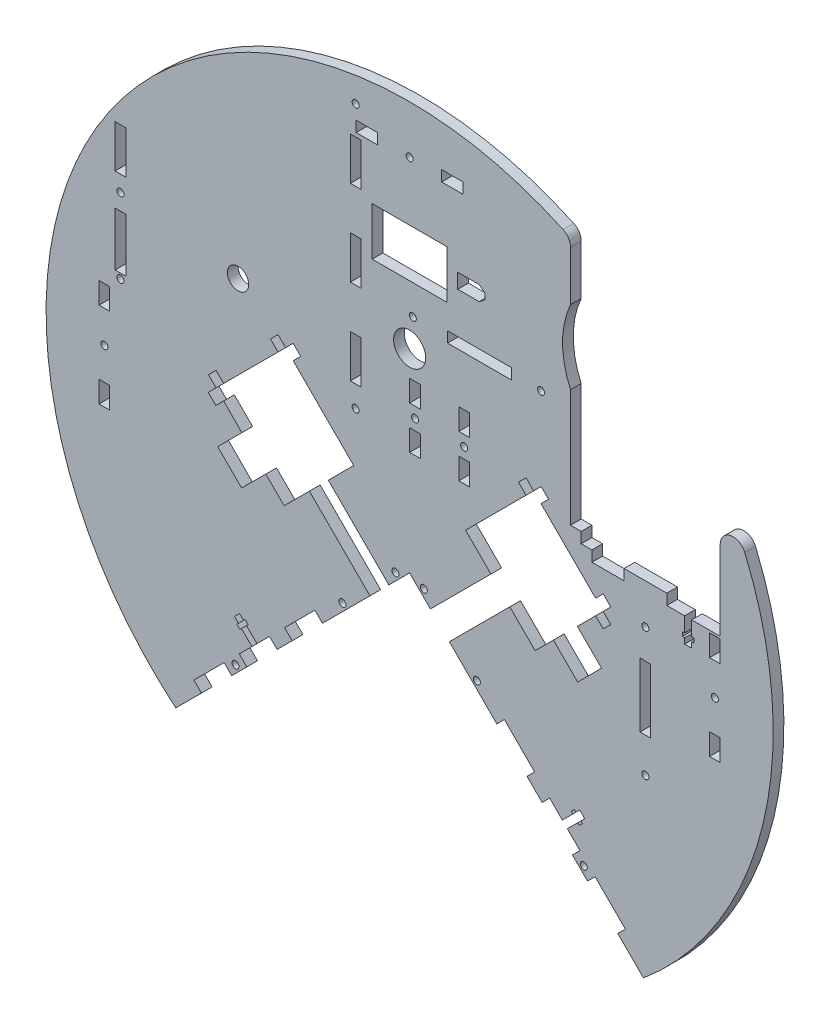
SolidWorks part; units mm, degrees
ref_plane "Front Plane" through (0, 0, 0) normal (0, 0, 1) x (1, 0, 0)
ref_plane "Top Plane" through (0, 0, 0) normal (0, 1, 0) x (1, 0, 0)
ref_plane "Right Plane" through (0, 0, 0) normal (1, 0, 0) x (0, 0, -1)
sketch "Sketch1" plane through (0, 0, 0) normal (0, 0, 1) x (1, 0, 0)
  circle A0 centre (0, 0) radius 215.9
  dimension "D1" = 431.8
extrude "Boss-Extrude1" add sketch "Sketch1" along normal blind 6.35 contours A0
sketch "Sketch2" plane through (0, 0, 0) normal (0, 0, -1) x (-1, 0, 0)
  line L0 (0, -26.4411) -> (138.8703, -165.3114)
  line L2 (0, -26.4411) -> (-138.8703, -165.3114)
  line L3 (-134.0557, -160.4967) -> (-35.731, -62.1721) construction
  line L4 (0, 0) -> (0, -240.5018) construction
  arc A4 (-138.8703, -165.3114) -> (138.8703, -165.3114) centre (0, 0) ccw
  circle A5 centre (0, 0) radius 215.9 construction
  dimension "D1" = 90
extrude "Cut-Extrude1" cut sketch "Sketch2" against normal through all
sketch "Sketch3" plane through (0, 0, 6.35) normal (0, 0, 1) x (1, 0, 0)
  line L0 (73.6381, 52.5852) -> (114.9473, 11.276)
  line L1 (73.6381, 52.5852) -> (33.2269, 12.174)
  line L2 (114.9473, 11.276) -> (74.5361, -29.1352)
  line L3 (33.2269, 12.174) -> (74.5361, -29.1352)
  line L4 (74.5361, -29.1352) -> (70.046, -24.645) construction
  line L5 (97.2507, 34.8885) -> (46.1575, -16.2046) construction
  line L6 (48.2689, -2.8679) -> (59.4942, -14.0932)
  line L7 (48.2689, -2.8679) -> (12.3479, -38.7889)
  line L8 (59.4942, -14.0932) -> (23.5732, -50.0143)
  line L9 (12.3479, -38.7889) -> (23.5732, -50.0143)
  line L10 (88.68, 15.0926) -> (77.4547, 26.3179) construction
  line L11 (0, -26.4411) -> (138.8703, -165.3114) construction
  line M8 (0, -26.4411) -> (138.8703, -165.3114)
extrude "Cut-Extrude2" cut sketch "Sketch3" against normal through all contours L8 L6 L3 L7 M8 | L0 L5 L6 L3 L2 | L5 L0 L1 L3 region at (63.7598, 22.0523, 6.35) region at (84.4144, 1.3977, 6.35) region at (35.921, -26.4411, 6.35)
mirror "Mirror1" about plane through (0, 0, 0) normal (1, 0, 0) of "Cut-Extrude2"
sketch "Sketch4" plane through (0, 0, 6.35) normal (0, 0, 1) x (1, 0, 0)
  line L0 (-178.0884, 19.05) -> (-178.0884, 31.75) construction
  line L1 (178.0884, -19.05) -> (184.4384, -19.05)
  line L2 (178.0884, -19.05) -> (178.0884, -31.75)
  line L3 (178.0884, -31.75) -> (184.4384, -31.75)
  line L4 (184.4384, -19.05) -> (184.4384, -31.75)
  line L5 (178.0884, 31.75) -> (184.4384, 31.75)
  line L6 (178.0884, 31.75) -> (178.0884, 19.05)
  line L7 (178.0884, 19.05) -> (184.4384, 19.05)
  line L8 (184.4384, 31.75) -> (184.4384, 19.05)
  line L9 (178.0884, -19.05) -> (184.4384, -19.05)
  line L10 (178.0884, -19.05) -> (178.0884, -31.75)
  line L11 (178.0884, -31.75) -> (184.4384, -31.75)
  line L12 (184.4384, -19.05) -> (184.4384, -31.75)
  line L13 (-184.4384, 31.75) -> (-178.0884, 31.75)
  line L14 (-184.4384, 31.75) -> (-184.4384, 19.05)
  line L15 (-184.4384, 19.05) -> (-178.0884, 19.05)
  line L16 (-178.0884, 31.75) -> (-178.0884, 19.05)
  line L18 (-184.4384, -19.05) -> (-178.0884, -19.05)
  line L19 (-184.4384, -19.05) -> (-184.4384, -31.75)
  line L20 (-184.4384, -31.75) -> (-178.0884, -31.75)
  line L21 (-178.0884, -19.05) -> (-178.0884, -31.75)
extrude "Cut-Extrude3" cut sketch "Sketch4" against normal through all contours L21 L18 L19 L20 | L8 L5 L6 L7 | L4 L1 L2 L3 | L14 L15 L16 L13 region at (181.2634, -25.4, 6.35) region at (181.2634, 25.4, 6.35) region at (-181.2634, -25.4, 6.35)
sketch "Sketch5" plane through (0, 0, 6.35) normal (0, 0, 1) x (1, 0, 0)
  line L0 (-128.1057, -145.5666) -> (-110.1452, -127.6061)
  line L1 (-110.1452, -127.6061) -> (-105.6551, -132.0962)
  line L2 (-138.8703, -165.3114) -> (-23.5732, -50.0143) construction
  line L3 (-105.6551, -132.0962) -> (-110.1452, -127.6061) construction
  line L4 (-105.6551, -132.0962) -> (-123.6156, -150.0567)
  line L5 (-128.1057, -145.5666) -> (-123.6156, -150.0567) construction
  line L6 (-123.6156, -150.0567) -> (-128.1057, -145.5666)
extrude "Cut-Extrude4" cut sketch "Sketch5" against normal blind 6.35
pattern_linear "LPattern1" count 3 spacing 38.1 along (0.7071, 0.7071, 0) of "Cut-Extrude4"
sketch "Sketch6" plane through (0, 0, 6.35) normal (0, 0, 1) x (1, 0, 0)
  line L0 (110.1452, -127.6061) -> (128.1057, -145.5666)
  line L1 (128.1057, -145.5666) -> (123.6156, -150.0567)
  line L2 (23.5732, -50.0143) -> (138.8703, -165.3114) construction
  line L3 (123.6156, -150.0567) -> (128.1057, -145.5666) construction
  line L4 (123.6156, -150.0567) -> (105.6551, -132.0962)
  line L5 (110.1452, -127.6061) -> (105.6551, -132.0962) construction
  line L6 (105.6551, -132.0962) -> (110.1452, -127.6061)
extrude "Cut-Extrude5" cut sketch "Sketch6" against normal blind 6.35
pattern_linear "LPattern2" count 3 spacing 38.1 along (-0.7071, 0.7071, 0) of "Cut-Extrude5"
sketch "Sketch8" plane through (0, 0, 0) normal (0, 0, -1) x (-1, 0, 0)
  line L0 (174.9134, 48.3833) -> (174.9134, 73.7833) construction
  line L1 (28.8634, 181.7333) -> (35.2134, 181.7333)
  line L2 (28.8634, 181.7333) -> (28.8634, 156.3333)
  line L3 (28.8634, 156.3333) -> (35.2134, 156.3333)
  line L4 (35.2134, 181.7333) -> (35.2134, 156.3333)
  line L5 (28.8634, 130.9333) -> (35.2134, 130.9333)
  line L6 (28.8634, 130.9333) -> (28.8634, 105.5333)
  line L7 (28.8634, 105.5333) -> (35.2134, 105.5333)
  line L8 (35.2134, 130.9333) -> (35.2134, 105.5333)
  line L9 (28.8634, 80.1333) -> (35.2134, 80.1333)
  line L10 (28.8634, 80.1333) -> (28.8634, 54.7333)
  line L11 (28.8634, 54.7333) -> (35.2134, 54.7333)
  line L12 (35.2134, 80.1333) -> (35.2134, 54.7333)
  line L13 (168.5634, 118.2333) -> (174.9134, 118.2333)
  line L14 (168.5634, 118.2333) -> (168.5634, 92.8333)
  line L15 (168.5634, 92.8333) -> (174.9134, 92.8333)
  line L16 (174.9134, 118.2333) -> (174.9134, 92.8333)
  line L17 (168.5634, 73.7833) -> (174.9134, 73.7833)
  line L18 (168.5634, 73.7833) -> (168.5634, 41.9385)
  line L19 (168.5634, 41.9385) -> (174.9134, 41.9385)
  line L20 (174.9134, 73.7833) -> (174.9134, 41.9385)
extrude "Cut-Extrude7" cut sketch "Sketch8" against normal through all
sketch "Sketch11" plane through (0, 0, 0) normal (0, 0, -1) x (-1, 0, 0)
  line L0 (184.4384, 2.1209) -> (178.0884, -2.1209) construction
  line L1 (184.4384, -2.1209) -> (178.0884, 2.1209) construction
  circle A0 centre (181.2634, 0) radius 2.0955
  dimension "D1" = 4.191
extrude "Wheel Hole" cut sketch "Sketch11" against normal through all
mirror "Mirror2" about plane through (0, 0, 0) normal (1, 0, 0) of "Wheel Hole"
sketch "Sketch12" plane through (0, 0, 6.35) normal (0, 0, 1) x (1, 0, 0)
  line L0 (0, 0) -> (0, 252.4228) construction
  line L1 (22.225, 123.825) -> (-22.225, 123.825)
  line L2 (22.225, 123.825) -> (22.225, 152.4)
  line L3 (22.225, 152.4) -> (-22.225, 152.4)
  line L4 (-22.225, 123.825) -> (-22.225, 152.4)
  arc A0 (138.8703, -165.3114) -> (-138.8703, -165.3114) centre (0, 0) ccw construction
  dimension "D3" = 152.4
  dimension "D1" = 28.575
  dimension "D2" = 44.45
extrude "Battery hole" cut sketch "Sketch12" against normal through all
sketch "Sketch13" plane through (0, 0, 0) normal (0, 0, -1) x (-1, 0, 0)
  line L0 (107.1638, -124.6246) -> (99.6563, -126.0974) construction
  line L1 (104.1464, -121.6073) -> (99.6563, -126.0974) construction
  line L2 (138.8703, -165.3114) -> (123.6156, -150.0567) construction
  line L3 (104.1464, -121.6073) -> (102.6737, -129.1148) construction
  line L4 (107.1638, -124.6246) -> (102.6737, -129.1148) construction
  line L5 (36.1647, -62.6058) -> (43.6722, -61.133) construction
  line L6 (51.7736, -78.2147) -> (23.5732, -50.0143) construction
  line L7 (40.6548, -58.1157) -> (36.1647, -62.6058) construction
  line L8 (39.1821, -65.6231) -> (40.6548, -58.1157) construction
  line L9 (43.6722, -61.133) -> (39.1821, -65.6231) construction
  line L10 (4.6652, -31.1063) -> (12.1727, -29.6336) construction
  line L11 (12.3479, -38.7889) -> (0, -26.4411) construction
  line L12 (9.1554, -26.6162) -> (4.6652, -31.1063) construction
  line L13 (7.6826, -34.1237) -> (9.1554, -26.6162) construction
  line L14 (12.1727, -29.6336) -> (7.6826, -34.1237) construction
  circle A0 centre (103.41, -125.361) radius 2.0955
  circle A1 centre (39.9184, -61.8694) radius 2.0955
  circle A2 centre (8.419, -30.37) radius 2.0955
  dimension "D1" = 4.191
extrude "Cut-Extrude10" cut sketch "Sketch13" against normal through all
mirror "Mirror3" about plane through (0, 0, 0) normal (1, 0, 0) of "Cut-Extrude10"
sketch "Sketch14" plane through (0, 0, 6.35) normal (0, 0, 1) x (1, 0, 0)
  line L0 (-174.9134, 85.4419) -> (-168.5634, 81.1747) construction
  line L1 (-168.5634, 85.4419) -> (-174.9134, 81.1747) construction
  line L2 (-174.9134, 40.9919) -> (-168.5634, 36.7247) construction
  line L3 (-174.9134, 36.7247) -> (-168.5634, 40.9919) construction
  circle A0 centre (-171.7384, 83.3083) radius 2.0955
  circle A1 centre (-171.7384, 38.8583) radius 2.0955
  dimension "D1" = 4.191
extrude "Cut-Extrude11" cut sketch "Sketch14" against normal through all
sketch "Sketch15" plane through (0, 0, 6.35) normal (0, 0, 1) x (1, 0, 0)
  line L0 (-28.8634, 44.1669) -> (-35.2134, 39.8997) construction
  line L1 (-35.2134, 44.1669) -> (-28.8634, 39.8997) construction
  line L2 (-35.2134, 200.9503) -> (-28.8634, 196.6831) construction
  line L3 (-28.8634, 200.9503) -> (-35.2134, 196.6831) construction
  circle A0 centre (-32.0384, 42.0333) radius 2.0955
  circle A1 centre (-32.0384, 198.8167) radius 2.0955
  dimension "D1" = 4.191
extrude "Cut-Extrude12" cut sketch "Sketch15" against normal through all
ref_axis "Axis1" through (0, 0, 465.2086) along (0, 0, -1)
sketch "Sketch21" plane through (0, 0, 6.35) normal (0, 0, 1) x (1, 0, 0)
  line L0 (36.8153, 138.1125) -> (56.9261, 138.1125) construction
  line L1 (22.225, 152.4) -> (-22.225, 152.4) construction
  line L2 (-22.225, 123.825) -> (22.225, 123.825) construction
  line L3 (41.275, 142.494) -> (44.831, 139.7953)
  line L4 (28.575, 142.494) -> (41.275, 142.494)
  line L5 (28.575, 142.494) -> (28.575, 133.731)
  line L6 (28.575, 133.731) -> (41.275, 133.731)
  line L7 (41.275, 142.494) -> (41.275, 133.731)
  line L8 (44.831, 139.7953) -> (44.831, 136.4297)
  line L9 (44.831, 136.4297) -> (41.275, 133.731)
  line L10 (22.225, 123.825) -> (22.225, 152.4) construction
  dimension "D1" = 8.763
  dimension "D2" = 12.7
  dimension "D3" = 3.3655
  dimension "D4" = 16.256
  dimension "D5" = 6.35
extrude "XT60BatteryHole" cut sketch "Sketch21" against normal through all contours L7 L4 L5 L6 | L9 L8 L3 L7 | L7 L0 L8 L3 region at (42.7892, 139.7286, 6.35) region at (34.925, 138.1125, 6.35) region at (42.7892, 136.4964, 6.35)
sketch "Sketch22" plane through (0, 0, 6.35) normal (0, 0, 1) x (1, 0, 0)
  line L0 (0, 0) -> (0, 99.9362) construction
  line L1 (-53.4325, 88.9) -> (53.4325, 88.9) construction
  circle A0 centre (0, 88.9) radius 9.525
  dimension "D1" = 19.05
  dimension "D2" = 88.9
extrude "Wire Hole for Servo and Top Comps." cut sketch "Sketch22" against normal through all
sketch "Sketch23" plane through (0, 0, 0) normal (0, 0, -1) x (-1, 0, 0)
  line L1 (-35.56, 35.56) -> (-29.21, 35.56)
  line L2 (-35.56, 35.56) -> (-35.56, 48.26)
  line L3 (-35.56, 48.26) -> (-29.21, 48.26)
  line L4 (-29.21, 35.56) -> (-29.21, 48.26)
  line L5 (-35.56, 60.96) -> (-29.21, 60.96)
  line L6 (-35.56, 60.96) -> (-35.56, 73.66)
  line L7 (-35.56, 73.66) -> (-29.21, 73.66)
  line L8 (-29.21, 60.96) -> (-29.21, 73.66)
  line L9 (-6.35, 35.56) -> (0, 35.56)
  line L10 (-6.35, 35.56) -> (-6.35, 48.26)
  line L11 (-6.35, 48.26) -> (0, 48.26)
  line L12 (0, 35.56) -> (0, 48.26)
  line L13 (-6.35, 60.96) -> (0, 60.96)
  line L14 (-6.35, 60.96) -> (-6.35, 73.66)
  line L15 (-6.35, 73.66) -> (0, 73.66)
  line L16 (0, 60.96) -> (0, 73.66)
extrude "CameraMountTabHoles" cut sketch "Sketch23" against normal through all
sketch "Sketch24" plane through (0, 0, 6.35) normal (0, 0, 1) x (1, 0, 0)
  line L0 (29.21, 56.7436) -> (35.56, 52.4764) construction
  line L1 (29.21, 52.4764) -> (35.56, 56.7436) construction
  line L2 (0, 56.7436) -> (6.35, 52.4764) construction
  line L3 (6.35, 56.7436) -> (0, 52.4764) construction
  circle A0 centre (32.385, 54.61) radius 2.0955
  circle A1 centre (3.175, 54.61) radius 2.0955
  dimension "D1" = 4.191
extrude "Cut-Extrude18" cut sketch "Sketch24" against normal through all
sketch "Sketch25" plane through (0, 0, 6.35) normal (0, 0, 1) x (1, 0, 0)
  line L1 (-31.75, 190.5) -> (-19.05, 190.5)
  line L2 (-31.75, 190.5) -> (-31.75, 184.15)
  line L3 (-31.75, 184.15) -> (-19.05, 184.15)
  line L4 (-19.05, 190.5) -> (-19.05, 184.15)
  line L5 (19.05, 190.5) -> (31.75, 190.5)
  line L6 (19.05, 190.5) -> (19.05, 184.15)
  line L7 (19.05, 184.15) -> (31.75, 184.15)
  line L8 (31.75, 190.5) -> (31.75, 184.15)
extrude "Cut-Extrude19" cut sketch "Sketch25" against normal through all
sketch "Sketch26" plane through (0, 0, 0) normal (0, 0, -1) x (-1, 0, 0)
  line L0 (-2.1336, 184.15) -> (2.1336, 190.5) construction
  line L1 (-2.1336, 190.5) -> (2.1336, 184.15) construction
  circle A0 centre (0, 187.325) radius 2.0955
  dimension "D1" = 4.191
extrude "Cut-Extrude20" cut sketch "Sketch26" against normal through all
sketch "Sketch27" plane through (0, 0, 6.35) normal (0, 0, 1) x (1, 0, 0)
  line L0 (167.1371, -38.3935) -> (160.7871, -34.1263) construction
  line L1 (167.1371, -34.1263) -> (160.7871, -38.3935) construction
  line L2 (167.1371, 58.5607) -> (160.7871, 62.8279) construction
  line L3 (167.1371, 62.8279) -> (160.7871, 58.5607) construction
  circle A0 centre (163.9621, 60.6943) radius 2.0955
  circle A1 centre (163.9621, -36.2599) radius 2.0955
  dimension "D1" = 4.191
extrude "Cut-Extrude21" [suppressed] cut sketch "Sketch27" against normal through all
sketch "Sketch28" plane through (0, 0, 6.35) normal (0, 0, 1) x (1, 0, 0)
  line L0 (28.2358, 111.125) -> (23.9686, 104.775) construction
  line L1 (23.9686, 111.125) -> (28.2358, 104.775) construction
  line L2 (125.19, 111.125) -> (120.9228, 104.775) construction
  line L3 (120.9228, 111.125) -> (125.19, 104.775) construction
  circle A0 centre (123.0564, 107.95) radius 2.0955
  circle A1 centre (26.1022, 107.95) radius 2.0955
  dimension "D1" = 4.191
extrude "Cut-Extrude22" [suppressed] cut sketch "Sketch28" against normal through all
sketch "Sketch29" plane through (0, 0, 0) normal (0, 0, -1) x (-1, 0, 0)
  line L1 (-167.1371, -11.1125) -> (-160.7871, -11.1125)
  line L2 (-167.1371, -11.1125) -> (-167.1371, 26.9875)
  line L3 (-167.1371, 26.9875) -> (-160.7871, 26.9875)
  line L4 (-160.7871, -11.1125) -> (-160.7871, 26.9875)
  line L5 (-89.3496, 111.125) -> (-51.2496, 111.125)
  line L6 (-89.3496, 111.125) -> (-89.3496, 104.775)
  line L7 (-89.3496, 104.775) -> (-51.2496, 104.775)
  line L8 (-51.2496, 111.125) -> (-51.2496, 104.775)
extrude "Cut-Extrude23" [suppressed] cut sketch "Sketch29" against normal through all
sketch "Sketch30" plane through (0, 0, 6.35) normal (0, 0, 1) x (1, 0, 0)
  line L0 (-92.1847, -109.6456) -> (-120.1804, -81.6499) construction
  line L1 (-83.2045, -100.6653) -> (-101.165, -118.6258) construction
  line L2 (-83.2045, -100.6653) -> (-101.165, -118.6258) construction
  line B0 (-93.6665, -111.1273) -> (-90.703, -108.1638)
  line B1 (-98.6954, -100.1714) -> (-97.7525, -99.2285)
  line B2 (-97.7525, -99.2285) -> (-95.9564, -101.0245)
  line B3 (-95.9564, -101.0245) -> (-96.8994, -101.9674)
  line B4 (-96.8994, -101.9674) -> (-90.703, -108.1638)
  line B5 (-98.6954, -100.1714) -> (-101.0303, -97.8365)
  line B6 (-101.0303, -97.8365) -> (-103.9938, -100.8)
  line B7 (-101.6589, -103.1349) -> (-103.9938, -100.8)
  line B8 (-99.8628, -104.9309) -> (-93.6665, -111.1273)
  line B9 (-100.8058, -105.8739) -> (-99.8628, -104.9309)
  line B10 (-102.6018, -104.0778) -> (-100.8058, -105.8739)
  line B11 (-101.6589, -103.1349) -> (-102.6018, -104.0778)
sketch_block_instance "TSlot-4"
sketch_block "TSlot" parameters "D1"=3.302, "D2"=2.54, "D3"=3.175, "D4"=8.763, "D5"=1.3462
extrude "Cut-Extrude24" cut sketch "Sketch30" against normal through all
mirror "Mirror4" about plane through (0, 0, 0) normal (1, 0, 0) of "Cut-Extrude24"
sketch "Sketch31" plane through (0, 0, 6.35) normal (0, 0, 1) x (1, 0, 0)
  line L0 (-99.591, -4.0803) -> (-85.4022, -18.2691)
  line L1 (-99.591, -4.0803) -> (-113.9595, -18.4487)
  line L2 (-85.4022, -18.2691) -> (-99.7706, -32.6375)
  line L3 (-113.9595, -18.4487) -> (-99.7706, -32.6375)
  line L4 (-114.9473, 11.276) -> (-74.5361, -29.1352) construction
  line L5 (-112.8988, -17.388) -> (-88.3298, 7.181) construction
  line L6 (-74.141, -7.0078) -> (-98.71, -31.5768) construction
  line L7 (-100.8313, -31.5768) -> (-112.8988, -19.5093) construction
  line L8 (99.591, -4.0803) -> (85.4022, -18.2691)
  line L9 (99.591, -4.0803) -> (113.9595, -18.4487)
  line L10 (85.4022, -18.2691) -> (99.7706, -32.6375)
  line L11 (113.9595, -18.4487) -> (99.7706, -32.6375)
  line L12 (114.9473, 11.276) -> (74.5361, -29.1352) construction
  line L14 (98.71, -31.5768) -> (74.141, -7.0078) construction
  line L15 (112.8988, -19.5093) -> (100.8313, -31.5768) construction
  line L16 (88.3298, 7.181) -> (112.8988, -17.388) construction
extrude "Cut-Extrude25" cut sketch "Sketch31" against normal through all
sketch "Sketch35" plane through (0, 0, 6.35) normal (0, 0, 1) x (1, 0, 0)
  line L0 (184.4384, 137.0763) -> (184.4384, 96.6763) construction
  line L1 (95.5384, 33.1763) -> (184.4384, 33.1763)
  line L2 (95.5384, 33.1763) -> (95.5384, 121.8763)
  line L4 (184.4384, 33.1763) -> (184.4384, 116.8763)
  line L5 (95.5384, 121.8763) -> (95.5384, 197.8088)
  arc A0 (95.5384, 197.8088) -> (184.4384, 116.8763) centre (14.0581, 19.0148) cw
extrude "Cut-Extrude28" cut sketch "Sketch35" against normal through all
fillet "Fillet2" radius 7.62 2 edges at (184.4384, 112.2287, 3.175) (95.5384, 193.611, 3.175)
sketch "Sketch36" plane through (95.5384, 0, 0) normal (1, 0, 0) x (0, 0, -1)
  line L0 (0, 188.8145) -> (0, 33.1763) construction
  line L1 (-6.35, 33.1763) -> (0, 33.1763)
  line L2 (-6.35, 33.1763) -> (-6.35, 45.8763)
  line L3 (-6.35, 45.8763) -> (0, 45.8763)
  line L4 (0, 33.1763) -> (0, 45.8763)
  line L5 (0, 45.8763) -> (-6.35, 45.8763) construction
extrude "Boss-Extrude8" add sketch "Sketch36" along normal blind 6.35
sketch "Sketch37" plane through (101.8884, 0, 0) normal (1, 0, 0) x (0, 0, -1)
  line L0 (-6.35, 45.8763) -> (-6.35, 33.1763) construction
  line L1 (-6.35, 39.5263) -> (0, 39.5263)
  line L2 (-6.35, 39.5263) -> (-6.35, 33.1763)
  line L3 (-6.35, 33.1763) -> (0, 33.1763)
  line L4 (0, 39.5263) -> (0, 33.1763)
extrude "Boss-Extrude9" add sketch "Sketch37" along normal blind 6.35
sketch "Sketch38" plane through (0, 0, 6.35) normal (0, 0, 1) x (1, 0, 0)
  line L0 (95.5384, 188.8145) -> (95.5384, 45.8763) construction
  line L1 (95.5384, 159.3081) -> (95.5384, 115.5739)
  arc A0 (95.5384, 115.5739) -> (95.5384, 159.3081) centre (143.7787, 137.441) cw
extrude "Cut-Extrude29" cut sketch "Sketch38" against normal through all
sketch "Sketch39" plane through (0, 0, 6.35) normal (0, 0, 1) x (1, 0, 0)
  line L0 (114.9473, 11.276) -> (119.4374, 6.7859)
  line L1 (114.9473, 11.276) -> (110.4572, 6.7859)
  line L2 (119.4374, 6.7859) -> (114.9473, 2.2957)
  line L3 (110.4572, 6.7859) -> (114.9473, 2.2957)
  line L4 (114.9473, 11.276) -> (110.4572, 15.7661)
  line L5 (114.9473, 11.276) -> (119.4374, 15.7661)
  line L6 (110.4572, 15.7661) -> (114.9473, 20.2562)
  line L7 (119.4374, 15.7661) -> (114.9473, 20.2562)
  line L8 (73.6381, 52.5852) -> (114.9473, 11.276) construction
  line L9 (110.4572, 15.7661) -> (105.967, 11.276) construction
  line L10 (73.6381, 52.5852) -> (78.0014, 48.2218)
  line L11 (73.6381, 52.5852) -> (78.1282, 57.0753)
  line L12 (78.0014, 48.2218) -> (82.4916, 52.712)
  line L13 (78.1282, 57.0753) -> (82.4916, 52.712)
  line L14 (73.6381, 52.5852) -> (69.148, 48.095)
  line L15 (73.6381, 52.5852) -> (69.148, 57.0753)
  line L16 (69.148, 48.095) -> (64.6578, 52.5852)
  line L17 (69.148, 57.0753) -> (64.6578, 52.5852)
  line L18 (73.6381, 52.5852) -> (33.2269, 12.174) construction
  line L19 (110.4572, 6.7859) -> (69.148, 48.095) construction
  line L20 (-73.6381, 52.5852) -> (-69.148, 48.095)
  line L21 (-73.6381, 52.5852) -> (-69.148, 57.0753)
  line L22 (-69.148, 48.095) -> (-64.6578, 52.5852)
  line L23 (-69.148, 57.0753) -> (-64.6578, 52.5852)
  line L24 (-73.6381, 52.5852) -> (-33.2269, 12.174) construction
  line L25 (-73.6381, 52.5852) -> (-78.1282, 57.0753)
  line L26 (-73.6381, 52.5852) -> (-78.1282, 48.095)
  line L27 (-78.1282, 57.0753) -> (-82.6184, 52.5852)
  line L28 (-78.1282, 48.095) -> (-82.6184, 52.5852)
  line L29 (-114.9473, 11.276) -> (-110.4572, 15.7661)
  line L30 (-114.9473, 11.276) -> (-119.4374, 15.7661)
  line L31 (-110.4572, 15.7661) -> (-114.9473, 20.2562)
  line L32 (-119.4374, 15.7661) -> (-114.9473, 20.2562)
  line L33 (-73.6381, 52.5852) -> (-114.9473, 11.276) construction
  line L34 (-114.9473, 11.276) -> (-110.4572, 6.7859)
  line L35 (-114.9473, 11.276) -> (-119.5658, 6.6575)
  line L36 (-110.4572, 6.7859) -> (-115.0757, 2.1674)
  line L37 (-119.5658, 6.6575) -> (-115.0757, 2.1674)
  line L38 (-114.9473, 11.276) -> (-99.591, -4.0803) construction
  line L39 (-110.4572, 6.7859) -> (-105.967, 11.276) construction
  dimension "D1" = 6.35
  dimension "D2" = 6.35
  dimension "D3" = 6.35
  dimension "D4" = 6.35
  dimension "D5" = 6.35
  dimension "D6" = 6.35
  dimension "D7" = 6.35
  dimension "D8" = 6.35
  dimension "D9" = 6.35
  dimension "D10" = 6.5316
  dimension "D11" = 6.35
  dimension "D12" = 6.35
extrude "Cut-Extrude30" cut sketch "Sketch39" against normal through all contours L23 L21 L20 L22 | L28 L26 L25 L27 | L35 L37 L36 L34 | L32 L30 L29 L31 | L15 L17 L16 L14 | L13 L11 L10 L12 | L5 L7 L6 L4 | L1 L3 L2 L0 region at (114.9473, 6.7859, 6.35) region at (114.9473, 15.7661, 6.35) region at (78.0648, 52.6486, 6.35) region at (69.148, 52.5852, 6.35) region at (-69.148, 52.5852, 6.35) region at (-78.1282, 52.5852, 6.35) region at (-114.9473, 15.7661, 6.35) region at (-115.0115, 6.7217, 6.35)
sketch "Sketch40" plane through (0, 33.1763, 0) normal (0, 1, 0) x (1, 0, 0)
  line L0 (108.2384, -6.35) -> (184.4384, -6.35) construction
  line L1 (127.2992, -6.35) -> (152.6884, -6.35)
  line L2 (127.2992, -6.35) -> (127.2992, 0)
  line L3 (127.2992, 0) -> (152.6884, 0)
  line L4 (152.6884, -6.35) -> (152.6884, 0)
  line L5 (108.2384, 0) -> (184.4384, 0) construction
extrude "Boss-Extrude10" add sketch "Sketch40" along normal blind 6.35
sketch "Sketch41" plane through (0, 0, 6.35) normal (0, 0, 1) x (1, 0, 0)
  line L0 (152.6884, 33.1763) -> (184.4384, 33.1763) construction
  line L1 (163.2929, 39.5263) -> (163.2929, 33.1763) construction
  line B0 (167.4839, 33.1763) -> (163.2929, 33.1763)
  line B1 (163.2929, 21.8733) -> (161.9594, 21.8733)
  line B2 (161.9594, 21.8733) -> (161.9594, 24.4133)
  line B3 (161.9594, 24.4133) -> (163.2929, 24.4133)
  line B4 (163.2929, 24.4133) -> (163.2929, 33.1763)
  line B5 (163.2929, 21.8733) -> (163.2929, 18.5713)
  line B6 (163.2929, 18.5713) -> (167.4839, 18.5713)
  line B7 (167.4839, 21.8733) -> (167.4839, 18.5713)
  line B8 (167.4839, 24.4133) -> (167.4839, 33.1763)
  line B9 (168.8174, 24.4133) -> (167.4839, 24.4133)
  line B10 (168.8174, 21.8733) -> (168.8174, 24.4133)
  line B11 (167.4839, 21.8733) -> (168.8174, 21.8733)
sketch_block_instance "TSlot-7"
extrude "Cut-Extrude31" cut sketch "Sketch41" against normal through all
sketch "Sketch42" plane through (0, 0, 0) normal (0, 0, -1) x (-1, 0, 0)
  line L1 (-136.8134, -39.8487) -> (-143.1634, -39.8487)
  line L2 (-136.8134, -39.8487) -> (-136.8134, -1.7487)
  line L3 (-136.8134, -1.7487) -> (-143.1634, -1.7487)
  line L4 (-143.1634, -39.8487) -> (-143.1634, -1.7487)
extrude "Cut-Extrude32" cut sketch "Sketch42" against normal through all
sketch "Sketch43" plane through (0, 0, 6.35) normal (0, 0, 1) x (1, 0, 0)
  line L0 (143.1634, -62.5817) -> (136.8134, -58.3907) construction
  line L1 (143.1634, -58.3907) -> (136.8134, -62.5817) construction
  line L2 (143.1634, 13.6183) -> (136.8134, 17.8093) construction
  line L3 (143.1634, 17.8093) -> (136.8134, 13.6183) construction
  circle A0 centre (139.9884, 15.7138) radius 2.0955
  circle A1 centre (139.9884, -60.4862) radius 2.0955
  dimension "D1" = 4.191
extrude "Cut-Extrude33" cut sketch "Sketch43" against normal through all
sketch "Sketch44" plane through (0, 0, 6.35) normal (0, 0, 1) x (1, 0, 0)
  line L0 (80.1714, 109.3763) -> (75.9804, 103.0263) construction
  line L1 (75.9804, 109.3763) -> (80.1714, 103.0263) construction
  line L2 (3.9714, 109.3763) -> (-0.2196, 103.0263) construction
  line L3 (-0.2196, 109.3763) -> (3.9714, 103.0263) construction
  circle A0 centre (78.0759, 106.2013) radius 2.0955
  circle A1 centre (1.8759, 106.2013) radius 2.0955
  dimension "D1" = 4.191
extrude "Cut-Extrude34" cut sketch "Sketch44" against normal through all
sketch "Sketch45" plane through (0, 0, 0) normal (0, 0, -1) x (-1, 0, 0)
  line L1 (-60.6134, 109.3763) -> (-22.5134, 109.3763)
  line L2 (-60.6134, 109.3763) -> (-60.6134, 103.0263)
  line L3 (-60.6134, 103.0263) -> (-22.5134, 103.0263)
  line L4 (-22.5134, 109.3763) -> (-22.5134, 103.0263)
extrude "Cut-Extrude35" cut sketch "Sketch45" against normal through all
sketch "Sketch46" plane through (0, 0, 6.35) normal (0, 0, 1) x (1, 0, 0)
  line L0 (-187.6134, 74.0248) -> (-16.1634, 74.0248) construction
  circle A0 centre (-101.8884, 74.0248) radius 6.35
  dimension "D1" = 12.7
extrude "Cut-Extrude36" cut sketch "Sketch46" against normal through all
